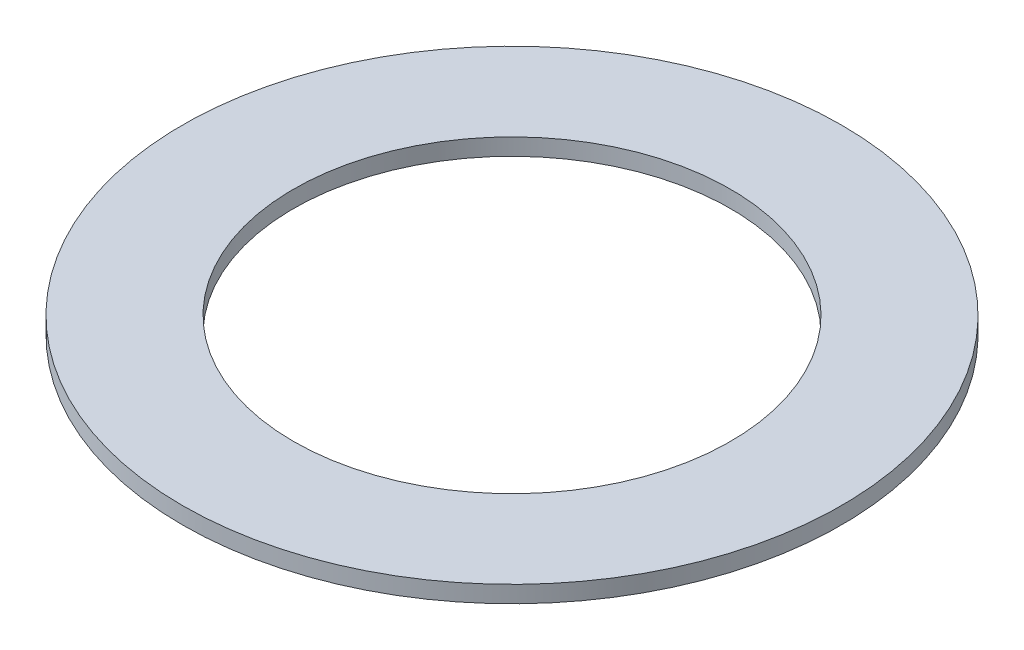
SolidWorks part; units mm, degrees
material "1060 Alloy"
ref_plane "Front Plane" through (0, 0, 0) normal (0, 0, 1) x (1, 0, 0)
ref_plane "Top Plane" through (0, 0, 0) normal (0, 1, 0) x (1, 0, 0)
ref_plane "Right Plane" through (0, 0, 0) normal (1, 0, 0) x (0, 0, -1)
sketch "Sketch1" plane through (0, 0, 0) normal (0, 1, 0) x (1, 0, 0)
  circle A0 centre (0, 0) radius 78.35
  circle A1 centre (0, 0) radius 49.55 construction
  circle A2 centre (0, 0) radius 51.95
  dimension "D1" = 156.7
  dimension "D2" = 99.1
  dimension "D3" = 2.4
extrude "Boss-Extrude1" add sketch "Sketch1" along normal blind 2 and the other way blind 2
